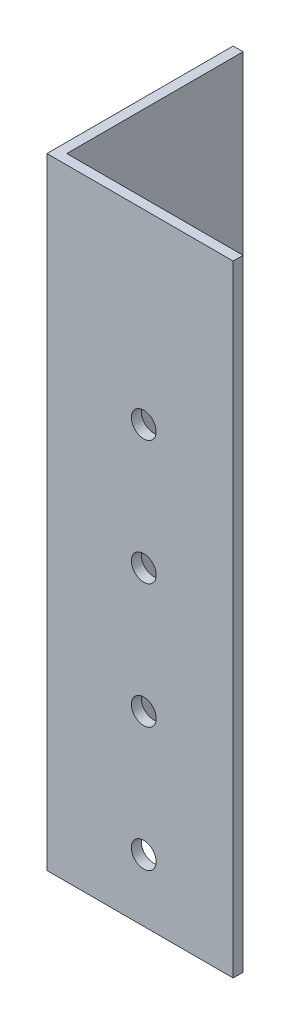
SolidWorks part; units mm, degrees
ref_plane "Спереди" through (0, 0, 0) normal (0, 0, 1) x (1, 0, 0)
ref_plane "Сверху" through (0, 0, 0) normal (0, 1, 0) x (1, 0, 0)
ref_plane "Справа" through (0, 0, 0) normal (1, 0, 0) x (0, 0, -1)
sketch "Эскиз1" plane through (0, 0, 0) normal (0, 1, 0) x (1, 0, 0)
  line L0 (0, 0) -> (75, 0)
  line L1 (0, 0) -> (0, 75)
extrude "Вытянуть-Тонкостенный1" add sketch "Эскиз1" along normal blind 250 thin thin type one direction wall 4
sketch "Эскиз6" plane through (0, 0, 0) normal (-1, 0, 0) x (0, 0, 1)
  circle A0 centre (-39, 25) radius 5
  circle A1 centre (-39, 75) radius 5
  circle A2 centre (-39, 125) radius 5
  circle A3 centre (-39, 175) radius 5
  dimension "D1" = 4
extrude "Вырез-Вытянуть1" cut sketch "Эскиз6" against normal blind 10
sketch "Эскиз7" plane through (0, 0, 0) normal (0, 0, 1) x (1, 0, 0)
  circle A0 centre (39, 25) radius 5
  circle A1 centre (39, 75) radius 5
  circle A2 centre (39, 125) radius 5
  circle A3 centre (39, 175) radius 5
  dimension "D1" = 4
extrude "Вырез-Вытянуть2" cut sketch "Эскиз7" against normal blind 10
